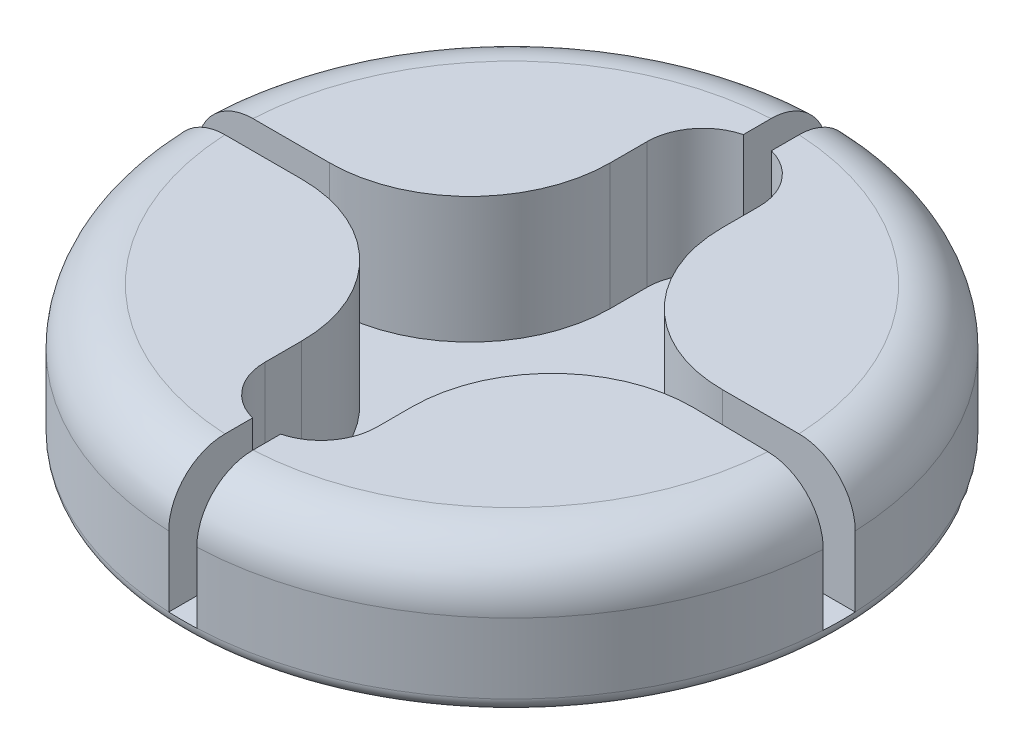
SolidWorks part; units mm, degrees
ref_plane "Plan de face" through (0, 0, 0) normal (0, 0, 1) x (1, 0, 0)
ref_plane "Plan de dessus" through (0, 0, 0) normal (0, 1, 0) x (1, 0, 0)
ref_plane "Plan de droite" through (0, 0, 0) normal (1, 0, 0) x (0, 0, -1)
sketch "Esquisse1" plane through (0, 0, 0) normal (0, 1, 0) x (1, 0, 0)
  circle A0 centre (0, 0) radius 23.5
extrude "Boss.-Extru.1" add sketch "Esquisse1" along normal blind 10
sketch "Esquisse2" plane through (0, 10, 0) normal (0, 1, 0) x (1, 0, 0)
  line L0 (0, 0) -> (0, 23.7585) construction
  line L1 (0, 0) -> (0, -23.5) construction
  line L2 (-23.5, 0) -> (4, 0) construction
  line L3 (0, 0) -> (-4, 0) construction
  line L4 (0, 0) -> (4, 0) construction
  line L5 (0, 0) -> (0, -17.4998) construction
  line L6 (0, 0) -> (0, 17.5002) construction
  line L7 (-1, 17.5002) -> (-4, 17.5002) construction
  line L8 (1, -17.4998) -> (4, -17.4998) construction
  line L9 (-4, -1) -> (-4, -17.4998)
  line L10 (-4, 17.5002) -> (-1, 17.5002)
  line L11 (-4, 17.5002) -> (-4, 1)
  line L12 (-4, -17.4998) -> (-1, -17.4998)
  line L13 (4, 17.5002) -> (4, 0.9998)
  line L14 (23.4787, 0) -> (23.5, 0) construction
  line L17 (4, -0.9998) -> (4, -17.4998)
  line L18 (23.5, 0) -> (23.4787, 0)
  line L27 (4, -0.9998) -> (23.9981, -1.2755)
  line L30 (4, 0) -> (23.4787, 0) construction
  line L31 (4, 0.9998) -> (23.9981, 0.9998)
  line L32 (23.9981, 0.9998) -> (23.9981, -1.2755)
  line L33 (-4, -1) -> (-24, -1)
  line L34 (-24, -1) -> (-24, 1)
  line L35 (-24, 1) -> (-4, 1)
  line L36 (1, -17.4998) -> (4, -17.4998)
  line L38 (1, -17.4998) -> (1, -24.4998)
  line L39 (1, -24.4998) -> (-1, -24.4998)
  line L40 (-1, -17.4998) -> (-1, -24.4998)
  line L41 (1, 17.5002) -> (4, 17.5002)
  line L43 (-1, 17.5002) -> (-1, 24.5002)
  line L44 (-1, 24.5002) -> (1, 24.5002)
  line L45 (1, 17.5002) -> (1, 24.5002)
  circle A0 centre (0, 0) radius 23.5 construction
  dimension "D3" = 7
  dimension "D1" = 35
  dimension "D2" = 8
  dimension "D4" = 2
  dimension "D5" = 2
  dimension "D6" = 7
  dimension "D7" = 2
sketch "Esquisse3" plane through (0, 0, 0) normal (0, -1, 0) x (1, 0, 0)
  line L1 (0.4379, 0) -> (0.4379, -4) construction
  line L2 (0.4379, 0) -> (0.4379, 8) construction
  line L3 (-22.0964, 8) -> (22.0964, 8) construction
  line L5 (0.4379, -4) -> (0.4379, -8) construction
  circle A0 centre (0, 0) radius 23.5 construction
  text T0 "Projet Eclipse\r\npar\r\nMaxime\r\nMAUCOURANT" font "Arial Rounded MT Bold" height in points 14
extrude "Boss.-Extru.2" add sketch "Esquisse3" along normal blind 1
extrude "Enlèv. mat.-Extru.5" cut sketch "Esquisse2" against normal blind 9
fillet "Congé3" radius 1 1 edges at (0, 0, 23.5)
fillet "Congé5" radius 10 4 edges at (-4, 5.5, -1) (-4, 5.5, 1) (4, 5.5, -0.9998) (4, 5.5, 0.9998)
fillet "Congé6" radius 4 4 edges at (4, 5.5, -17.5002) (-4, 5.5, -17.5002) (-4, 5.5, 17.4998) (4, 5.5, 17.4998)
fillet "Congé7" radius 4 4 edges at (16.5218, 10, 16.7117) (16.6171, 10, -16.6169) (-16.617, 10, -16.617) (-16.617, 10, 16.617)
